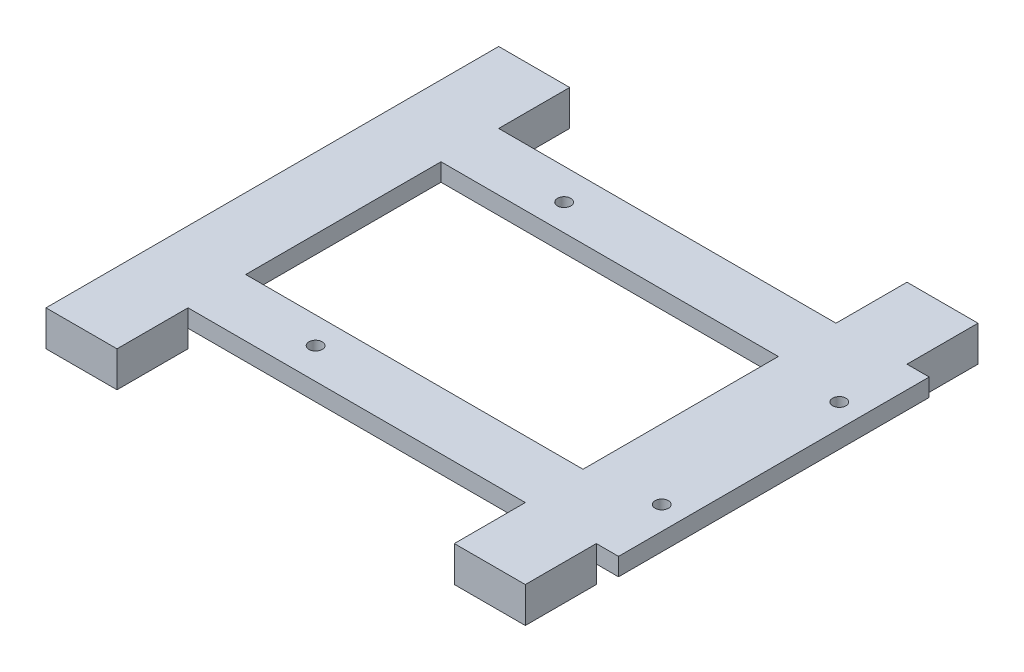
SolidWorks part; units mm, degrees
ref_plane "Front Plane" through (0, 0, 0) normal (0, 0, 1) x (1, 0, 0)
ref_plane "Top Plane" through (0, 0, 0) normal (0, 1, 0) x (1, 0, 0)
ref_plane "Right Plane" through (0, 0, 0) normal (1, 0, 0) x (0, 0, -1)
sketch "Sketch1" plane through (0, 0, 0) normal (0, 1, 0) x (1, 0, 0)
  line L1 (-56.5, 35) -> (56.5, 35)
  line L2 (-56.5, 35) -> (-56.5, -35)
  line L3 (-56.5, -35) -> (56.5, -35)
  line L4 (56.5, 35) -> (56.5, -35)
  line L5 (-56.5, 35) -> (56.5, -35) construction
  line L6 (-56.5, -35) -> (56.5, 35) construction
  point P0 (0, 0)
  dimension "D1" = 113
  dimension "D2" = 70
extrude "Boss-Extrude1" add sketch "Sketch1" along normal blind 4
sketch "Sketch2" plane through (0, 4, 0) normal (0, 1, 0) x (1, 0, 0)
  line L0 (0, 35) -> (0, -35) construction
  line L1 (56.5, 35) -> (-56.5, 35) construction
  line L2 (-56.5, -35) -> (56.5, -35) construction
  line L4 (-56.5, 0) -> (56.5, 0) construction
  line L5 (-56.5, 35) -> (-56.5, -35) construction
  line L6 (56.5, -35) -> (56.5, 35) construction
  circle A46 centre (-18.75, 28) radius 1.5
  circle A47 centre (-18.75, -28) radius 1.5
  circle A48 centre (51.25, -20) radius 1.5
  circle A49 centre (51.25, 20) radius 1.5
  point P20 (-90.5401, -28.4577)
  point P21 (0, 0)
  point P22 (0, 0)
  point P23 (0, 0)
  line B0 (-25.4814, 0) -> (70.4814, 0) construction
  arc B1 (-19.5394, -30.8943) -> (-19.2077, -30.9649) centre (-18.75, -28) ccw construction
  arc B2 (-21.6443, -28.7894) -> (-19.5394, -30.8943) centre (-18.75, -28) ccw construction
  arc B3 (-21.7149, -28.4577) -> (-21.6443, -28.7894) centre (-18.75, -28) ccw construction
  arc B4 (-19.2077, 30.9649) -> (-19.5394, 30.8943) centre (-18.75, 28) ccw construction
  arc B5 (-19.5394, 30.8943) -> (-21.6443, 28.7894) centre (-18.75, 28) ccw construction
  arc B6 (-21.6443, 28.7894) -> (-21.7149, 28.4577) centre (-18.75, 28) ccw construction
  arc B7 (-21.7149, 28.4577) -> (-21.7149, -28.4577) centre (83.9083, 0) ccw construction
  arc B8 (-19.2077, -30.9649) -> (9.25, -34.7314) centre (9.25, 74.6583) ccw construction
  arc B9 (9.25, -34.7314) -> (63.3655, -15.1715) centre (9.25, 49.9083) ccw construction
  arc B10 (63.3655, -15.1715) -> (63.3655, 15.1715) centre (50.75, 0) ccw construction
  arc B11 (63.3655, 15.1715) -> (9.25, 34.7314) centre (9.25, -49.9083) ccw construction
  arc B12 (9.25, 34.7314) -> (-19.2077, 30.9649) centre (9.25, -74.6583) ccw construction
  arc B13 (51.25, 22.5132) -> (51.25, 17.4868) centre (51.25, 20) ccw construction
  arc B14 (51.25, 17.5) -> (51.25, 22.5) centre (51.25, 20) ccw construction
  arc B15 (51.25, -17.5) -> (51.25, -22.5) centre (51.25, -20) ccw construction
  arc B16 (51.25, -22.5132) -> (51.25, -17.4868) centre (51.25, -20) ccw construction
  arc B17 (-18.75, -25.5) -> (-18.75, -30.5) centre (-18.75, -28) ccw construction
  arc B18 (-18.75, -30.5132) -> (-18.75, -25.4868) centre (-18.75, -28) ccw construction
  arc B19 (-18.75, 30.5) -> (-18.75, 25.5) centre (-18.75, 28) ccw construction
  arc B20 (-18.75, 25.5) -> (-18.75, 30.5) centre (-18.75, 28) ccw construction
  dimension "D1" = 3
  dimension "D2" = 3
  dimension "D3" = 3
  dimension "D4" = 3
  dimension "D5" = 34
sketch_block_instance "Block2-1"
sketch_block "Block2"
extrude "Cut-Extrude1" cut sketch "Sketch2" against normal through all contours A46 | A49 | A47 | A48
sketch "Sketch4" plane through (0, 0, 0) normal (0, -1, 0) x (1, 0, 0)
  line L0 (-56.5, 35) -> (56.5, 35) construction
  line L5 (-56.5, 35) -> (-40.5, 35)
  line L6 (-56.5, 35) -> (-56.5, 51)
  line L7 (-56.5, 51) -> (-40.5, 51)
  line L8 (-40.5, 35) -> (-40.5, 51)
  line L9 (51.5, 35) -> (35.5, 35)
  line L10 (51.5, 35) -> (51.5, 51)
  line L11 (51.5, 51) -> (35.5, 51)
  line L12 (35.5, 35) -> (35.5, 51)
  line L18 (56.5, 35) -> (56.5, -35) construction
  line L19 (0, 0) -> (-56.5, 0) construction
  line L20 (-56.5, -35) -> (-56.5, 35) construction
  line L21 (51.5, -51) -> (35.5, -51)
  line L22 (35.5, -35) -> (35.5, -51)
  line L23 (51.5, -35) -> (35.5, -35)
  line L24 (51.5, -35) -> (51.5, -51)
  line L25 (-56.5, -51) -> (-40.5, -51)
  line L26 (-40.5, -35) -> (-40.5, -51)
  line L27 (-56.5, -35) -> (-40.5, -35)
  line L28 (-56.5, -35) -> (-56.5, -51)
  dimension "D1" = 16
  dimension "D2" = 16
  dimension "D3" = 5
  dimension "D4" = 16
  dimension "D5" = 16
extrude "Boss-Extrude3" add sketch "Sketch4" against normal up to surface (4 mm away) and the other way blind 1 up to face at (-18.75, 4, -26.5)
sketch "Sketch6" plane through (0, 4, 0) normal (0, 1, 0) x (1, 0, 0)
  line L0 (-40.5, -35) -> (-40.5, -51) construction
  line L1 (-40.5, 22) -> (35.5, 22)
  line L2 (-40.5, 22) -> (-40.5, -22)
  line L3 (-40.5, -22) -> (35.5, -22)
  line L4 (35.5, 22) -> (35.5, -22)
  line L5 (35.5, -51) -> (35.5, -35) construction
  line L6 (35.5, 35) -> (-40.5, 35) construction
  line L7 (-40.5, -35) -> (35.5, -35) construction
  dimension "D1" = 13
  dimension "D2" = 13
extrude "Cut-Extrude2" cut sketch "Sketch6" against normal through all
sketch "Sketch8" plane through (0, -1, 0) normal (0, -1, 0) x (1, 0, 0)
  line L0 (-56.5, 51) -> (-40.5, 51) construction
  line L1 (-56.5, 51) -> (-56.5, 35) construction
  line L2 (-56.5, 35) -> (-40.5, 35) construction
  line L3 (-40.5, 51) -> (-40.5, 35) construction
  line L4 (35.5, 51) -> (51.5, 51) construction
  line L5 (35.5, 51) -> (35.5, 35) construction
  line L6 (35.5, 35) -> (51.5, 35) construction
  line L7 (51.5, 51) -> (51.5, 35) construction
  line L8 (-56.5, 51) -> (-40.5, 35) construction
  line L9 (-56.5, 35) -> (-40.5, 51) construction
  line L10 (35.5, 51) -> (51.5, 35) construction
  line L11 (35.5, 35) -> (51.5, 51) construction
  line L12 (51.5, 51) -> (35.5, 51) construction
  line L13 (0, 0) -> (-56.5, 0) construction
  line L14 (-56.5, 35) -> (-40.5, 35) construction
  line L15 (35.5, 35) -> (51.5, 35) construction
  circle A0 centre (-48.5, 43) radius 6.1
  circle A1 centre (43.5, 43) radius 6.1
  circle A2 centre (43.5, -43) radius 6.1
  circle A3 centre (-48.5, -43) radius 6.1
  dimension "D3" = 12.2
  dimension "D4" = 12.2
extrude "Cut-Extrude3" cut sketch "Sketch8" against normal blind 3.2
sketch "Sketch9" plane through (0, -1, 0) normal (0, -1, 0) x (1, 0, 0)
  line L0 (-55.5, 50) -> (-55.5, 36)
  line L1 (-56.5, 51) -> (-40.5, 51)
  line L2 (-56.5, 51) -> (-56.5, 35)
  line L3 (-56.5, 35) -> (-40.5, 35)
  line L4 (-40.5, 51) -> (-40.5, 35)
  line L5 (35.5, 51) -> (51.5, 51)
  line L6 (35.5, 51) -> (35.5, 35)
  line L7 (35.5, 35) -> (51.5, 35)
  line L8 (51.5, 51) -> (51.5, 35)
  line L9 (-55.5, 36) -> (-41.5, 36)
  line L10 (-41.5, 50) -> (-41.5, 36)
  line L11 (-55.5, 50) -> (-41.5, 50)
  line L16 (0, 0) -> (-56.5, 0) construction
  line L17 (36.5, -36) -> (50.5, -36)
  line L18 (36.5, -50) -> (36.5, -36)
  line L19 (50.5, -50) -> (36.5, -50)
  line L20 (50.5, 36) -> (50.5, 50)
  line L21 (50.5, 50) -> (36.5, 50)
  line L22 (36.5, 50) -> (36.5, 36)
  line L23 (36.5, 36) -> (50.5, 36)
  line L24 (50.5, 36) -> (50.5, 50)
  line L25 (50.5, 50) -> (36.5, 50)
  line L26 (36.5, 50) -> (36.5, 36)
  line L27 (36.5, 36) -> (50.5, 36)
  line L28 (50.5, -36) -> (50.5, -50)
  line L29 (-55.5, -50) -> (-41.5, -50)
  line L30 (-41.5, -50) -> (-41.5, -36)
  line L31 (-55.5, -36) -> (-41.5, -36)
  line L32 (51.5, -51) -> (51.5, -35)
  line L33 (35.5, -35) -> (51.5, -35)
  line L34 (35.5, -51) -> (35.5, -35)
  line L35 (35.5, -51) -> (51.5, -51)
  line L36 (-40.5, -51) -> (-40.5, -35)
  line L37 (-56.5, -35) -> (-40.5, -35)
  line L38 (-56.5, -51) -> (-56.5, -35)
  line L39 (-56.5, -51) -> (-40.5, -51)
  line L40 (-55.5, -50) -> (-55.5, -36)
  dimension "D1" = 1
  dimension "D2" = 1
extrude "Boss-Extrude5" add sketch "Sketch9" along normal blind 3
fillet "Fillet1" radius 0.2 4 edges at (43.5, -1, -36.9) (-48.5, -1, -36.9) (43.5, -1, 36.9) (-48.5, -1, 36.9)
